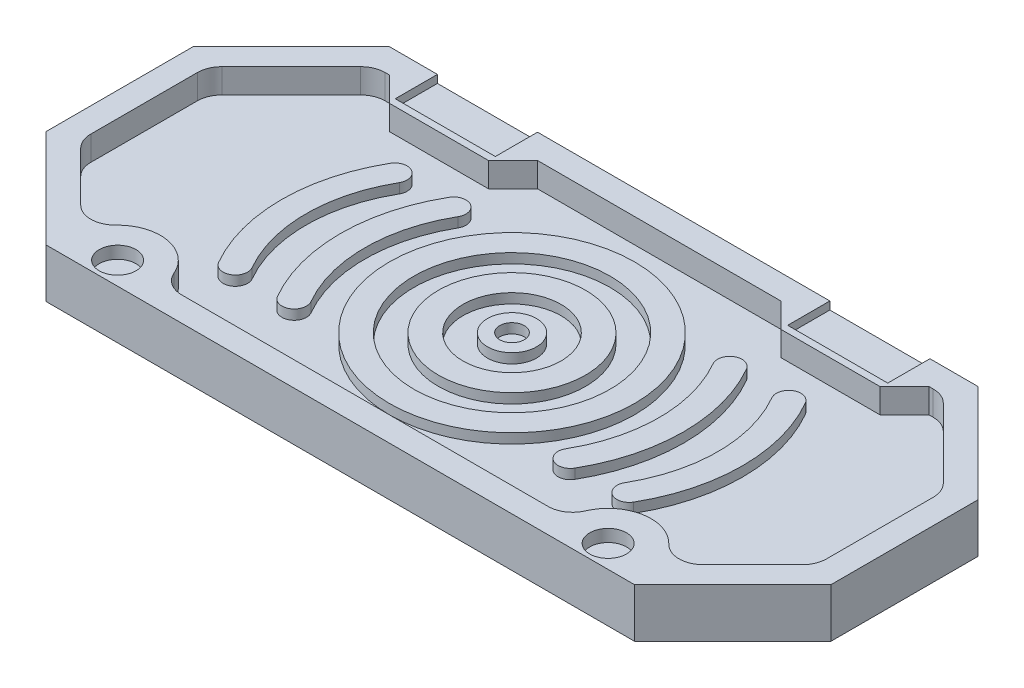
SolidWorks part; units mm, degrees
ref_plane "前视基准面" through (0, 0, 0) normal (0, 0, 1) x (1, 0, 0)
ref_plane "上视基准面" through (0, 0, 0) normal (0, 1, 0) x (1, 0, 0)
ref_plane "右视基准面" through (0, 0, 0) normal (1, 0, 0) x (0, 0, -1)
other "Configuration Table"
sketch "Sketch1" plane through (0, 0, 0) normal (0, 1, 0) x (1, 0, 0)
  line L0 (-76.2, 44.45) -> (-101.6, 19.05)
  line L1 (-76.2, 44.45) -> (76.2, 44.45)
  line L2 (-101.6, 19.05) -> (-101.6, -19.05)
  line L3 (-76.2, -44.45) -> (76.2, -44.45)
  line L4 (101.6, 19.05) -> (101.6, -19.05)
  line L5 (-101.6, 44.45) -> (101.6, -44.45) construction
  line L6 (-101.6, -44.45) -> (101.6, 44.45) construction
  line L7 (-101.6, -19.05) -> (-76.2, -44.45)
  line L8 (76.2, 44.45) -> (101.6, 19.05)
  line L9 (101.6, -19.05) -> (76.2, -44.45)
  arc A0 (76.2, -44.45) -> (101.6, -19.05) centre (76.2, -19.05) ccw construction
  arc A1 (101.6, 19.05) -> (76.2, 44.45) centre (76.2, 19.05) ccw construction
  arc A2 (-76.2, -44.45) -> (-101.6, -19.05) centre (-76.2, -19.05) cw construction
  arc A3 (-101.6, 19.05) -> (-76.2, 44.45) centre (-76.2, 19.05) cw construction
  point P0 (0, 0)
  dimension "D3" = 25.4
  dimension "D1" = 88.9
  dimension "D2" = 203.2
extrude "Boss-Extrude1" add sketch "Sketch1" along normal blind 12.7
sketch "Sketch2" plane through (0, 12.7, 0) normal (0, 1, 0) x (1, 0, 0)
  line L0 (-76.2, -44.45) -> (76.2, -44.45) construction
  line L2 (-101.6, 19.05) -> (-101.6, -19.05) construction
  circle A0 centre (-63.5, -38.608) radius 4.7625
  dimension "D3" = 9.525
  dimension "D1" = 5.842
  dimension "D2" = 38.1
extrude "Cut-Extrude1" cut sketch "Sketch2" against normal blind 3.175
mirror "Mirror1" about plane through (0, 0, 0) normal (1, 0, 0) of "Cut-Extrude1"
shell "Shell2" thickness 6.35 removed face at (63.5, 12.7, 43.3705)
fillet "Fillet3" radius 6.35 10 edges at (-52.3991, 9.525, 38.1) (52.3991, 9.525, 38.1) (95.25, 9.525, 16.4197) (95.25, 9.525, -16.4197) (73.5697, 9.525, -38.1) (-73.5697, 9.525, -38.1) (-95.25, 9.525, -16.4197) (-95.25, 9.525, 16.4197) (74.5168, 9.525, 37.1529) (-74.5168, 9.525, 37.1529)
sketch "Sketch3" plane through (0, 6.35, 0) normal (0, 1, 0) x (1, 0, 0)
  line L0 (-76.2, 44.45) -> (-63.5, 31.75)
  line L1 (-63.5, 31.75) -> (63.5, 31.75)
  line L2 (63.5, 31.75) -> (76.2, 44.45)
  line L3 (-76.2, 44.45) -> (-101.6, 19.05) construction
  line L4 (101.6, 19.05) -> (76.2, 44.45) construction
  line L5 (-76.2, 44.45) -> (76.2, 44.45)
  dimension "D1" = 90
  dimension "D2" = 90
  dimension "D3" = 127
extrude "Boss-Extrude2" add sketch "Sketch3" along normal blind 6.35
sketch "Sketch4" plane through (0, 6.35, 0) normal (0, 1, 0) x (1, 0, 0)
  line L0 (76.2, 44.45) -> (-76.2, 44.45) construction
  line L1 (-63.754, 44.45) -> (-37.846, 44.45)
  line L2 (-63.754, 44.45) -> (-63.754, 33.528)
  line L3 (-63.754, 33.528) -> (-37.846, 33.528)
  line L4 (-37.846, 44.45) -> (-37.846, 33.528)
  line L5 (-63.754, 44.45) -> (-37.846, 33.528) construction
  line L6 (-63.754, 33.528) -> (-37.846, 44.45) construction
  point P4 (-50.8, 38.989)
  dimension "D1" = 25.4
  dimension "D2" = 25.908
  dimension "D3" = 10.922
extrude "Cut-Extrude2" cut sketch "Sketch4" against normal blind 2.032 from surface starting at face at (0, 12.7, 0)
mirror "Mirror2" about plane through (0, 0, 0) normal (1, 0, 0) of "Cut-Extrude2"
sketch "Sketch5" plane through (0, 12.7, 0) normal (0, 1, 0) x (1, 0, 0)
  line L0 (-37.846, 31.75) -> (-31.496, 38.1)
  line L1 (-63.5, 31.75) -> (63.5, 31.75) construction
  line L2 (-31.496, 38.1) -> (31.496, 38.1)
  line L3 (31.496, 38.1) -> (37.846, 31.75)
  line L4 (-63.5, 31.75) -> (63.5, 31.75) construction
  line L5 (70.9395, 38.1) -> (69.85, 38.1) construction
  line L6 (-37.846, 31.75) -> (37.846, 31.75)
  dimension "D1" = 45
  dimension "D2" = 45
extrude "Cut-Extrude3" cut sketch "Sketch5" against normal up to surface (6.35 mm away) up to face at (0, 6.35, -1.0365)
sketch "Sketch6" plane through (0, 6.35, 0) normal (0, 1, 0) x (1, 0, 0)
  line L1 (31.496, 38.1) -> (-31.496, 38.1) construction
  circle A0 centre (0, 0) radius 31.75
  circle A1 centre (0, 0) radius 25.4
  dimension "D2" = 50.8
  dimension "D1" = 6.35
extrude "Boss-Extrude3" add sketch "Sketch6" along normal blind 2.54
sketch "Sketch7" plane through (0, 6.35, 0) normal (0, 1, 0) x (1, 0, 0)
  circle A0 centre (0, 0) radius 19.05
  circle A1 centre (0, 0) radius 25.4 construction
  circle A2 centre (0, 0) radius 12.7
  dimension "D1" = 6.35
  dimension "D2" = 6.35
extrude "Boss-Extrude4" add sketch "Sketch7" along normal blind 2.54
sketch "Sketch8" plane through (0, 6.35, 0) normal (0, 1, 0) x (1, 0, 0)
  circle A0 centre (0, 0) radius 6.35
  circle A1 centre (0, 0) radius 12.7 construction
  circle A2 centre (0, 0) radius 3.175
  dimension "D1" = 6.35
  dimension "D2" = 6.35
extrude "Boss-Extrude5" add sketch "Sketch8" along normal blind 2.54
sketch "Sketch9" plane through (0, 6.35, 0) normal (0, 1, 0) x (1, 0, 0)
  line L0 (-35.7452, 20.6375) -> (0, 0) construction
  line L1 (0, 0) -> (-35.7452, -20.6375) construction
  line L4 (0, 0) -> (-41.275, 0) construction
  arc A0 (-35.7452, 20.6375) -> (-35.7452, -20.6375) centre (0, 0) ccw construction
  arc A1 (-38.4948, 22.225) -> (-38.4948, -22.225) centre (0, 0) ccw
  arc A2 (-32.9956, 19.05) -> (-32.9956, -19.05) centre (0, 0) ccw
  arc A3 (-32.9956, 19.05) -> (-38.4948, 22.225) centre (-35.7452, 20.6375) ccw
  arc A4 (-38.4948, -22.225) -> (-32.9956, -19.05) centre (-35.7452, -20.6375) ccw
  point P4 (-41.275, 0)
  dimension "D2" = 3.175
  dimension "D3" = 38.1
  dimension "D4" = 60
extrude "Boss-Extrude6" add sketch "Sketch9" along normal blind 2.54
pattern_linear "LPattern1" count 2 spacing 15.24 along (-1, 0, 0) of "Boss-Extrude6"
mirror "Mirror3" about plane through (0, 0, 0) normal (1, 0, 0) of "Boss-Extrude6", "LPattern1"
